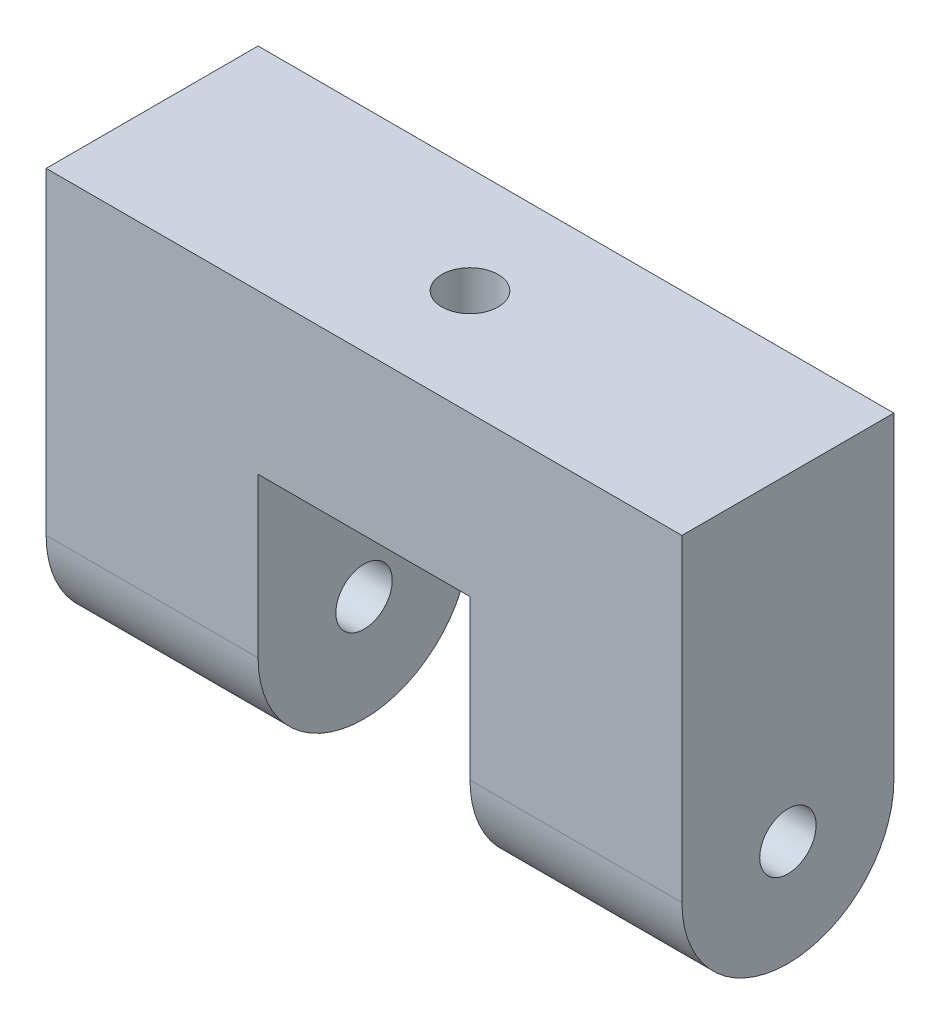
SolidWorks part; units mm, degrees
ref_plane "Front Plane" through (0, 0, 0) normal (0, 0, 1) x (1, 0, 0)
ref_plane "Top Plane" through (0, 0, 0) normal (0, 1, 0) x (1, 0, 0)
ref_plane "Right Plane" through (0, 0, 0) normal (1, 0, 0) x (0, 0, -1)
sketch "Sketch1" plane through (0, 0, 0) normal (0, 1, 0) x (1, 0, 0)
  line L0 (-12.7, 12.7) -> (-12.7, -12.7)
  line L1 (-38.1, 12.7) -> (38.1, 12.7)
  line L2 (-38.1, 12.7) -> (-38.1, -12.7)
  line L3 (-38.1, -12.7) -> (38.1, -12.7)
  line L4 (38.1, 12.7) -> (38.1, -12.7)
  line L5 (-38.1, 12.7) -> (38.1, -12.7) construction
  line L6 (-38.1, -12.7) -> (38.1, 12.7) construction
  line L7 (12.7, 12.7) -> (12.7, -12.7)
  dimension "D1" = 25.4
  dimension "D2" = 76.2
  dimension "D4" = 25.4
  dimension "D5" = 25.4
extrude "Boss-Extrude1" add sketch "Sketch1" along normal blind 19.05 contours L7 L1 L0 L3 | L1 L7 L3 L4 | L2 L3 L0 L1 region at (0, 0, 0) region at (-25.4, 0, 0) region at (25.4, 0, 0)
extrude "Boss-Extrude3" add sketch "Sketch1<7>" against normal blind 31.75 contours L2 L3 L0 L1 | L1 L7 L3 L4 region at (-25.4, 0, 0) region at (25.4, 0, 0)
sketch "Sketch1<7>" plane through (0, 0, 0) normal (0, 1, 0) x (1, 0, 0) same geometry as "Sketch1"
sketch "Sketch2" plane through (-38.1, 0, 0) normal (-1, 0, 0) x (0, 0, 1)
  line L0 (-12.7, -31.75) -> (12.7, -31.75) construction
  line L1 (0, 19.05) -> (0, -31.75) construction
  line L2 (-12.7, 19.05) -> (12.7, 19.05) construction
  circle A0 centre (0, -19.05) radius 3.3782
  dimension "D2" = 6.7564
  dimension "D1" = 12.7
extrude "Cut-Extrude4" cut sketch "Sketch2" against normal through all contours L1 A0 | A0 L1 region at (-38.1, -19.05, 1.4338) region at (-38.1, -19.05, -1.4338)
sketch "Sketch3" plane through (0, 19.05, 0) normal (0, 1, 0) x (1, 0, 0)
  circle A0 centre (0, 0) radius 3.3782
  dimension "D1" = 6.7564
fillet "Fillet1" radius 12.7 4 edges at (-25.4, -31.75, 12.7) (25.4, -31.75, 12.7) (25.4, -31.75, -12.7) (-25.4, -31.75, -12.7)
extrude "Cut-Extrude5" cut sketch "Sketch3" against normal through all
ref_plane "Plane2" through (0, 9.525, 0) normal (0, -1, 0) x (-1, 0, 0)
sketch "Sketch4" plane through (0, 9.525, 0) normal (0, -1, 0) x (-1, 0, 0)
  line L1 (3.2996, -5.715) -> (6.5991, 0)
  line L2 (6.5991, 0) -> (3.2996, 5.715)
  line L3 (3.2996, 5.715) -> (-3.2996, 5.715)
  line L4 (-3.2996, 5.715) -> (-6.5991, 0)
  line L5 (-6.5991, 0) -> (-3.2996, -5.715)
  line L6 (-3.2996, -5.715) -> (3.2996, -5.715)
  line L7 (6.5991, 0) -> (6.5991, 12.7)
  line L8 (6.5991, 12.7) -> (-6.5991, 12.7)
  line L9 (-6.5991, 12.7) -> (-6.5991, 0)
  line L11 (12.7, -12.7) -> (-12.7, -12.7) construction
  line L12 (12.7, 12.7) -> (-12.7, 12.7) construction
  circle A0 centre (0, 0) radius 5.715 construction
  dimension "D1" = 11.43
extrude "Cut-Extrude6" cut sketch "Sketch4" against normal mid plane 8.89 contours L8 L9 L4 L3 L2 L7 | L5 L6 L1 L2 L3 L4 region at (0, 9.525, 0) region at (0, 9.525, -8.2909)
